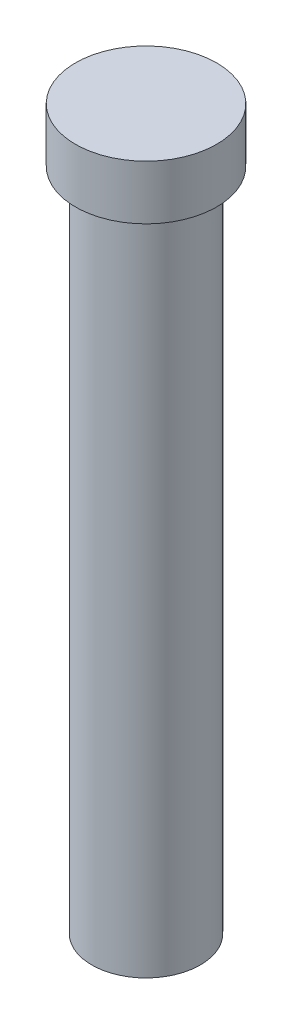
SolidWorks part; units mm, degrees
material "M2 HSS"
ref_plane "Front Plane" through (0, 0, 0) normal (0, 0, 1) x (1, 0, 0)
ref_plane "Top Plane" through (0, 0, 0) normal (0, 1, 0) x (1, 0, 0)
ref_plane "Right Plane" through (0, 0, 0) normal (1, 0, 0) x (0, 0, -1)
sketch "Sketch1" plane through (0, 0, 0) normal (0, 0, 1) x (1, 0, 0)
  line L0 (0, 0) -> (6.5, 0)
  line L1 (6.5, 0) -> (6.5, -5)
  line L2 (6.5, -5) -> (5, -5)
  line L3 (5, -5) -> (5, -66.2)
  line L4 (5, -66.2) -> (0, -66.2)
  line L5 (0, -66.2) -> (0, 0)
  line L6 (0, -71.2) -> (0, 5) construction
  dimension "D1" = 5
  dimension "D2" = 66.2
  dimension "D3" = 5
  dimension "D4" = 5
  dimension "D5" = 10
  dimension "D6" = 13
revolve "Revolve1" add sketch "Sketch1" angle 360 about L6
